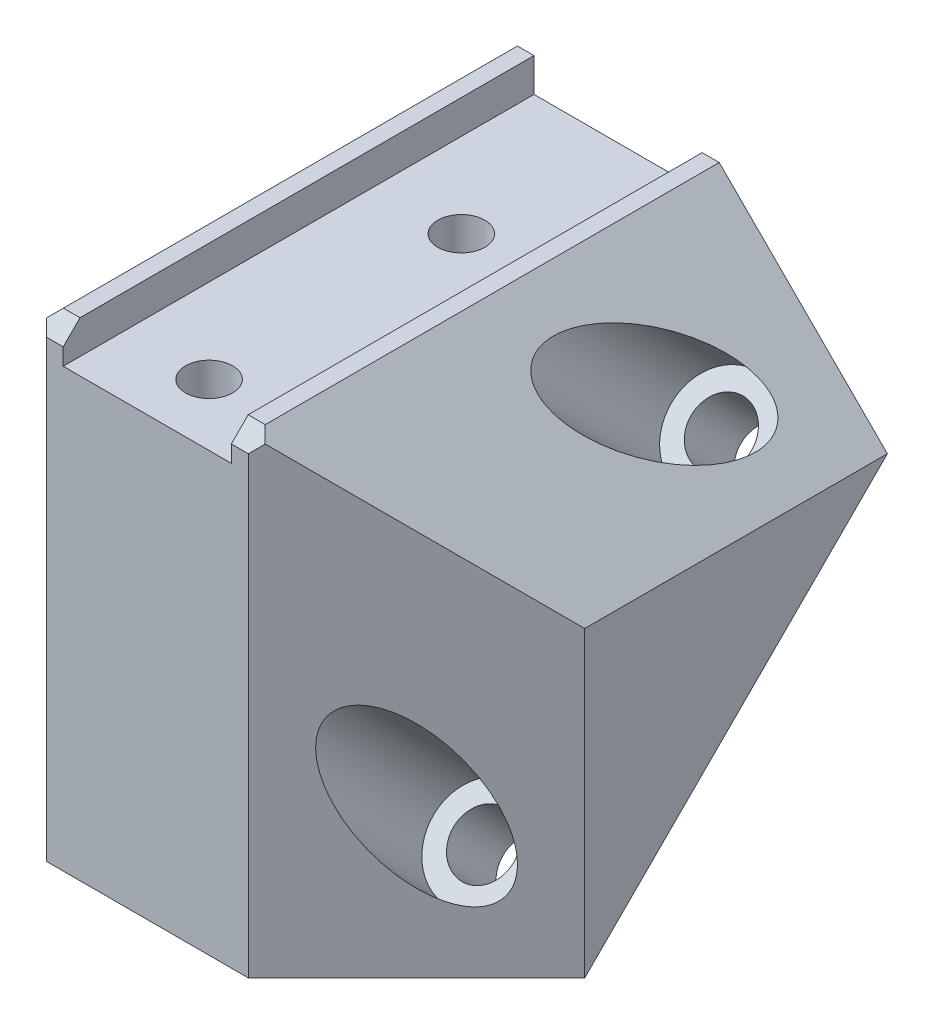
SolidWorks part; units mm, degrees
ref_plane "Front Plane" through (0, 0, 0) normal (0, 0, 1) x (1, 0, 0)
ref_plane "Top Plane" through (0, 0, 0) normal (0, 1, 0) x (1, 0, 0)
ref_plane "Right Plane" through (0, 0, 0) normal (1, 0, 0) x (0, 0, -1)
sketch "Sketch1" plane through (0, 0, 0) normal (1, 0, 0) x (0, 0, -1)
  line L1 (0, 0) -> (-28, 0)
  line L2 (0, 0) -> (0, 28)
  line L3 (0, 28) -> (-28, 28)
  line L4 (-28, 0) -> (-28, 28)
  dimension "D1" = 28
  dimension "D2" = 28
extrude "Boss-Extrude1" add sketch "Sketch1" along normal blind 32
chamfer "Chamfer1" distance 18 angle 45 1 edges at (16, 0, 0)
sketch "Sketch2" plane through (0, 28, 0) normal (0, 1, 0) x (1, 0, 0)
  circle A0 centre (16, -9.338) radius 1.4
  circle A1 centre (16, -24.338) radius 1.4
  dimension "D1" = 2.8
  dimension "D2" = 16
extrude "Cut-Extrude1" cut sketch "Sketch2" against normal blind 5.5
chamfer "Chamfer2" distance 1 angle 45 1 edges at (16, 28, 28)
sketch "Sketch3" plane through (0, 9, 9) normal (0, -0.7071, -0.7071) x (-1, 0, 0)
  circle A0 centre (-5, -10) radius 1.8
  circle A1 centre (-27, -10) radius 1.8
  circle A2 centre (-27, 10) radius 1.8
  circle A3 centre (-5, 10) radius 1.8
  dimension "D1" = 3.6
  dimension "D2" = 20
  dimension "D3" = 10
  dimension "D4" = 22
  dimension "D5" = 5
extrude "Cut-Extrude2" cut sketch "Sketch3" against normal through all
sketch "Sketch4" plane through (0, 27.5, 27.5) normal (0, 0.7071, 0.7071) x (1, 0, 0)
  circle A0 centre (5, 10) radius 3
  circle A1 centre (27, 10) radius 3
  circle A2 centre (27, -10) radius 3
  circle A3 centre (5, -10) radius 3
  dimension "D1" = 6
extrude "Cut-Extrude3" cut sketch "Sketch4" against normal blind 22
chamfer "Chamfer3" distance 10 angle 45 4 edges at (0, 28, 13.5) (0, 13.5, 28) (32, 13.5, 28) (32, 28, 13.5)
sketch "Sketch5" plane through (0, 28, 0) normal (0, 1, 0) x (1, 0, 0)
  line L0 (22, 0) -> (10, 0) construction
  line L1 (10.9863, 0) -> (20.9863, 0)
  line L2 (10.9863, 0) -> (10.9863, -28)
  line L3 (10.9863, -28) -> (20.9863, -28)
  line L4 (20.9863, 0) -> (20.9863, -28)
  line L6 (22, -28) -> (10, -28) construction
  point P6 (20.8585, -28)
  point P8 (21.0516, -27)
  point P10 (20.9863, -28)
  point P12 (20.9067, 0)
  dimension "D1" = 10
extrude "Cut-Extrude4" cut sketch "Sketch5" against normal blind 2 contours L2 L3 L4 L1
